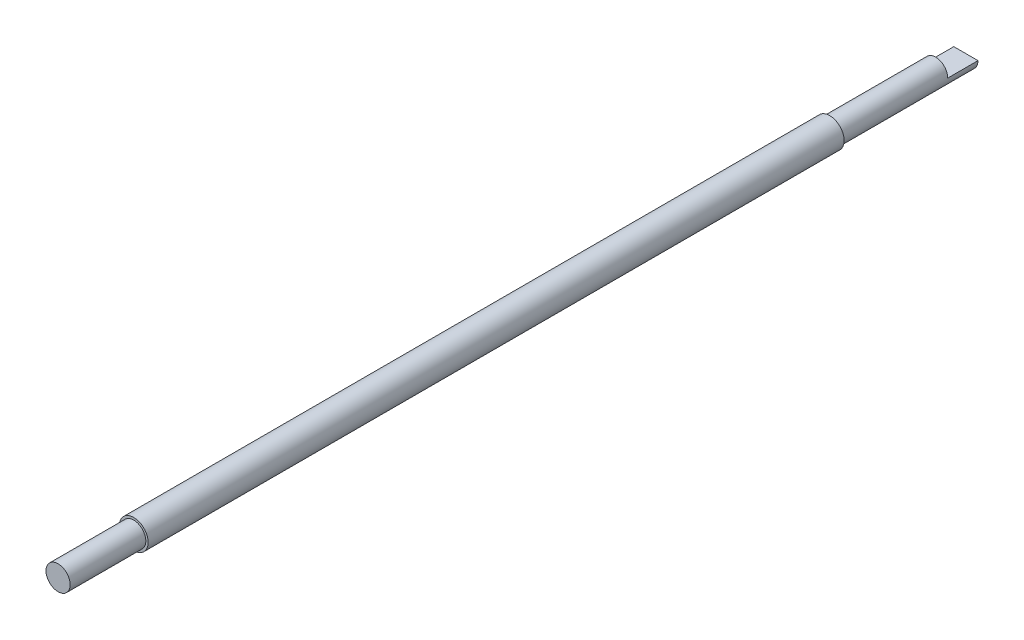
SolidWorks part; units mm, degrees
ref_plane "Front Plane" through (0, 0, 0) normal (0, 0, 1) x (1, 0, 0)
ref_plane "Top Plane" through (0, 0, 0) normal (0, 1, 0) x (1, 0, 0)
ref_plane "Right Plane" through (0, 0, 0) normal (1, 0, 0) x (0, 0, -1)
sketch "Sketch1" plane through (0, 0, 0) normal (0, 0, 1) x (1, 0, 0)
  circle A0 centre (0, 0) radius 4.7625
  dimension "D1" = 9.525
extrude "Boss-Extrude1" add sketch "Sketch1" along normal blind 300
sketch "Sketch3" plane through (0, 0, 0) normal (0, 0, -1) x (-1, 0, 0)
  circle A0 centre (0, 0) radius 4.7625
  circle A1 centre (0, 0) radius 4
  dimension "D1" = 9.525
  dimension "D2" = 8
extrude "Cut-Extrude2" cut sketch "Sketch3" against normal blind 45
sketch "Sketch4" plane through (0, 0, 0) normal (0, 0, -1) x (-1, 0, 0)
  line L0 (-4, 0) -> (4, 0)
  circle A0 centre (0, 0) radius 4 construction
  circle A1 centre (0, 0) radius 4 construction
  circle A2 centre (0, 0) radius 4
  circle M2 centre (0, 0) radius 4
  dimension "D1" = 8
  dimension "D2" = 8
extrude "Cut-Extrude3" cut sketch "Sketch4" against normal blind 10 contours L0 M2 region at (0, 1.6977, 0)
sketch "Sketch5" plane through (0, 0, 300) normal (0, 0, 1) x (1, 0, 0)
  circle A0 centre (0, 0) radius 4
  circle A1 centre (0, 0) radius 4.7625
  dimension "D1" = 8
  dimension "D2" = 9.525
extrude "Cut-Extrude4" cut sketch "Sketch5" against normal blind 25
